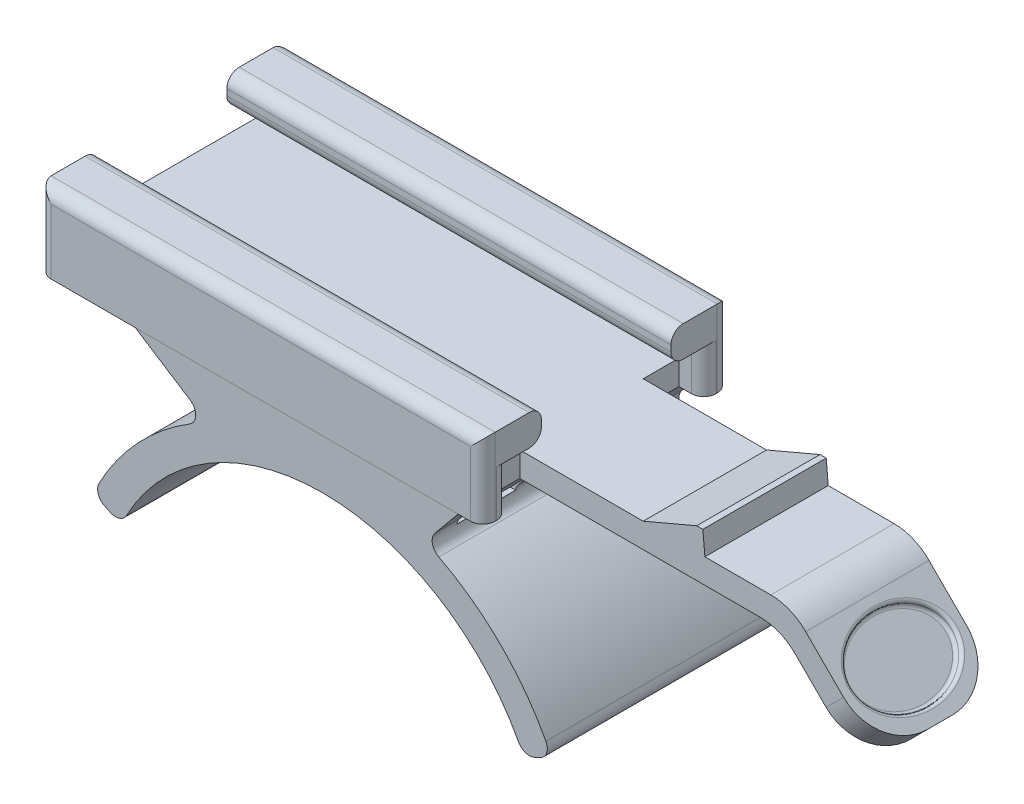
SolidWorks part; units mm, degrees
ref_plane "Front Plane" through (0, 0, 0) normal (0, 0, 1) x (1, 0, 0)
ref_plane "Top Plane" through (0, 0, 0) normal (0, 1, 0) x (1, 0, 0)
ref_plane "Right Plane" through (0, 0, 0) normal (1, 0, 0) x (0, 0, -1)
ref_axis "Axis1" through (-33.0333, 0, 0) along (1, 0, 0)
ref_axis "Axis2" through (0, 24.5224, 0) along (0, -1, 0)
ref_axis "Axis3" through (0, 0, -30.7663) along (0, 0, 1)
sketch "Sketch1" plane through (0, 0, 0) normal (0, 1, 0) x (1, 0, 0)
  line L0 (0, 0) -> (18, 0) construction
  line L1 (-18, -10) -> (18, -10)
  line L2 (-18, -10) -> (-18, 10)
  line L3 (-18, 10) -> (18, 10)
  line L5 (-18, -10) -> (18, 10) construction
  line L6 (-18, 10) -> (18, -10) construction
  line L7 (18, 7.9) -> (18, -7.9) construction
  line L8 (18, 10) -> (18, 7.9)
  line L9 (18, 7.9) -> (16, 7.9)
  line L11 (16, -7.9) -> (18, -7.9)
  line L12 (18, -7.9) -> (18, -10)
  line L18 (16, 7.9) -> (16, 5)
  line L19 (16, 5) -> (38, 5)
  line L20 (38, 5) -> (38, -5)
  line L21 (38, -5) -> (16, -5)
  line L22 (16, -5) -> (16, -7.9)
  point P0 (0, 0)
  point P11 (18, 0)
  dimension "D1" = 20
  dimension "D2" = 36
  dimension "D3" = 10
  dimension "D4" = 20
  dimension "D5" = 2.1
  dimension "D6" = 2
extrude "Boss-Extrude1" add sketch "Sketch1" along normal blind 2
sketch "Sketch2" plane through (0, 2, 0.1358) normal (0, 1, 0) x (0, 0, 1)
  line L0 (-3.8858, 0) -> (-0.1358, 0) construction
  line L3 (-10.1358, 18) -> (-8.0358, 18) construction
  line L7 (-10.1358, 18) -> (-10.1358, -18)
  line L10 (-10.1358, -18) -> (-8.0358, -18)
  line L15 (9.8642, -18) -> (7.7642, -18)
  line L18 (-10.1358, 18) -> (-8.0358, 18)
  line L25 (-8.0358, 18) -> (-8.0358, -18)
  line L26 (7.7642, -18) -> (7.7642, 18)
  line L27 (7.7642, 18) -> (9.8642, 18)
  line L29 (9.8642, 18) -> (9.8642, -18)
extrude "Boss-Extrude2" add sketch "Sketch2" along normal blind 1.75
sketch "Sketch3" plane through (0, 3.75, 0) normal (0, 1, 0) x (1, 0, 0)
  line L13 (-18, 10) -> (18, 10)
  line L20 (-18, 10) -> (-18, 5.25)
  line L21 (-18, 5.25) -> (18, 5.25)
  line L22 (18, 10) -> (18, 5.25)
  line L25 (-18, -10) -> (18, -10)
  line L26 (-18, -10) -> (-18, -5.25)
  line L37 (-18, -5.25) -> (18, -5.25)
  line L38 (18, -10) -> (18, -5.25)
  dimension "D1" = 4.75
extrude "Boss-Extrude3" add sketch "Sketch3" along normal blind 2.5
sketch "Sketch11" plane through (0, 0, 0) normal (0, 0, 1) x (1, 0, 0)
  line L1 (30.8381, 3.85) -> (31, 2)
  line L2 (31, 2) -> (26, 2)
  line L3 (16, 2) -> (-18, 2) construction
  line L4 (31, 2) -> (33.5, 2) construction
  line L5 (30.8381, 3.85) -> (30.3381, 3.85)
  line L6 (30.3381, 3.85) -> (26, 2)
  line L7 (16, 2) -> (38, 2) construction
  line L8 (-18, 0) -> (31, 0) construction
  line L10 (16, 0) -> (38, 0) construction
  line L11 (31, 0) -> (31, 2) construction
  dimension "D1" = 1.85
  dimension "D2" = 2.5
  dimension "D3" = 5
  dimension "D4" = 85
  dimension "D5" = 0.5
  dimension "D6" = 49
extrude "Boss-Extrude9" add sketch "Sketch11" along normal up to vertex (-5 mm away) and the other way up to vertex (-5 mm away) up to point (38, 2, -5) other way up to point (16, 2, 5)
sketch "Sketch12" plane through (0, 0, 5) normal (0, 0, 1) x (1, 0, 0)
  line L0 (38, 2) -> (45.0711, -5.0711)
  line L1 (45.0711, -5.0711) -> (43.6569, -6.4853)
  line L2 (43.6569, -6.4853) -> (37.1716, 0)
  line L5 (34.5, 2) -> (34.5, 0) construction
  line L6 (31, 2) -> (38, 2) construction
  line L7 (16, 0) -> (38, 0) construction
  line L8 (37.1716, 0) -> (38, 2)
  dimension "D1" = 10
  dimension "D2" = 45
extrude "Boss-Extrude10" add sketch "Sketch12" against normal up to surface (10 mm away) up to face at (28.272, 1.9625, -5)
fillet "Fillet2" radius 4 2 edges at (44.364, -5.7782, -5) (44.364, -5.7782, 5)
fillet "Fillet3" radius 4 2 edges at (37.1716, 0, 0) (38, 2, 0)
sketch "Sketch13" plane through (20, 20, 0) normal (0.7071, 0.7071, 0) x (0, 0, -1)
  line L0 (-5, -27.1127) -> (5, -27.1127) construction
  line L1 (0, -27.1127) -> (0, -31.1885) construction
  line L2 (0, -31.1885) -> (4.133, -31.1885) construction
  line L3 (0, -31.1885) -> (0, -34.3294) construction
  ellipse E0 centre (0, -31.1885) end of major axis (4.133, -31.1885) minor radius 3.1409
  point P14 (0, 0)
  point P15 (-4.133, -31.1885)
extrude "Cut-Extrude1" cut sketch "Sketch13" against normal blind 0.5
fillet "Fillet4" radius 0.25 2 edges at (42.0536, -2.0536, 4.133) (41.7, -2.4071, 4.133)
fillet "Fillet1" radius 1 12 edges at (-18, 3.125, -10) (18, 3.125, -10) (18, 1.875, -7.9) (18, 1.875, 7.9) (18, 3.125, 10) (-18, 3.125, 10) (0, 6.25, 5.25) (0, 6.25, -5.25) (0, 3.75, 5.25) (0, 3.75, -5.25) (0, 6.25, -10) (0, 6.25, 10)
sketch "Sketch14" plane through (0, 0, 0) normal (0, 0, 1) x (1, 0, 0)
  line L0 (-11.3135, -14.3929) -> (-13.5793, -13.3363)
  line L1 (21.3135, -14.3929) -> (23.5793, -13.3363)
  line L2 (5, -22) -> (0, 0) construction
  line L3 (-17, 0) -> (17, 0) construction
  line L4 (-10.1719, 0) -> (-4.3393, -3.751)
  line L5 (5, -22) -> (5, 0) construction
  line L7 (-10.1719, 0) -> (16, 0)
  line L8 (-9.5559, -22) -> (19.5559, -22) construction
  line L9 (16, 0) -> (13.3046, -3.2575)
  line L10 (16, 2) -> (16, 0) construction
  circle A0 centre (5, -22) radius 18 construction
  arc A1 (-11.3135, -14.3929) -> (21.3135, -14.3929) centre (5, -22) cw
  arc A2 (-13.5793, -13.3363) -> (-4.3393, -3.751) centre (5, -22) cw
  arc A3 (13.3046, -3.2575) -> (23.5793, -13.3363) centre (5, -22) cw
  point P12 (5, -22)
  dimension "D1" = 36
  dimension "D2" = 2.5
  dimension "D3" = 25
  dimension "D4" = 25
  dimension "D6" = 22
  dimension "D7" = 5
extrude "Boss-Extrude11" add sketch "Sketch14" along normal up to surface and the other way up to surface separate body up to face at (0, 2.625, 10) other way up to face at (0, 2.625, -10)
fillet "Fillet5" radius 1 2 edges at (13.3046, -3.2575, 0) (-4.3393, -3.751, 0)
sketch "Sketch15" plane through (0, 0, 0) normal (1, 0, 0) x (0, 0, -1)
  line L0 (0, 0) -> (0, -2) construction
  line L1 (-5.625, -2) -> (5.625, -2) construction
  line L2 (10, -4.5457) -> (10, -2.8532) construction
  line L3 (-8, -2.75) -> (-3.25, -2.75)
  line L4 (-8, -2.75) -> (-8, -1.25)
  line L5 (-8, -1.25) -> (-3.25, -1.25)
  line L6 (-3.25, -2.75) -> (-3.25, -1.25)
  line L7 (-8, -2.75) -> (-3.25, -1.25) construction
  line L8 (-8, -1.25) -> (-3.25, -2.75) construction
  line L9 (3.25, -2.75) -> (8, -2.75)
  line L10 (3.25, -2.75) -> (3.25, -1.25)
  line L11 (3.25, -1.25) -> (8, -1.25)
  line L12 (8, -2.75) -> (8, -1.25)
  line L13 (3.25, -2.75) -> (8, -1.25) construction
  line L14 (3.25, -1.25) -> (8, -2.75) construction
  point P5 (0, -2)
  dimension "D1" = 4.75
  dimension "D2" = 1.5
  dimension "D3" = 2
  dimension "D4" = 2
extrude "Cut-Extrude2" cut sketch "Sketch15" against normal blind 17.85 and the other way blind 25.85
fillet "Fillet6" radius 1 4 edges at (-13.5793, -13.3363, 0) (-11.3135, -14.3929, 0) (21.3135, -14.3929, 0) (23.5793, -13.3363, 0)
